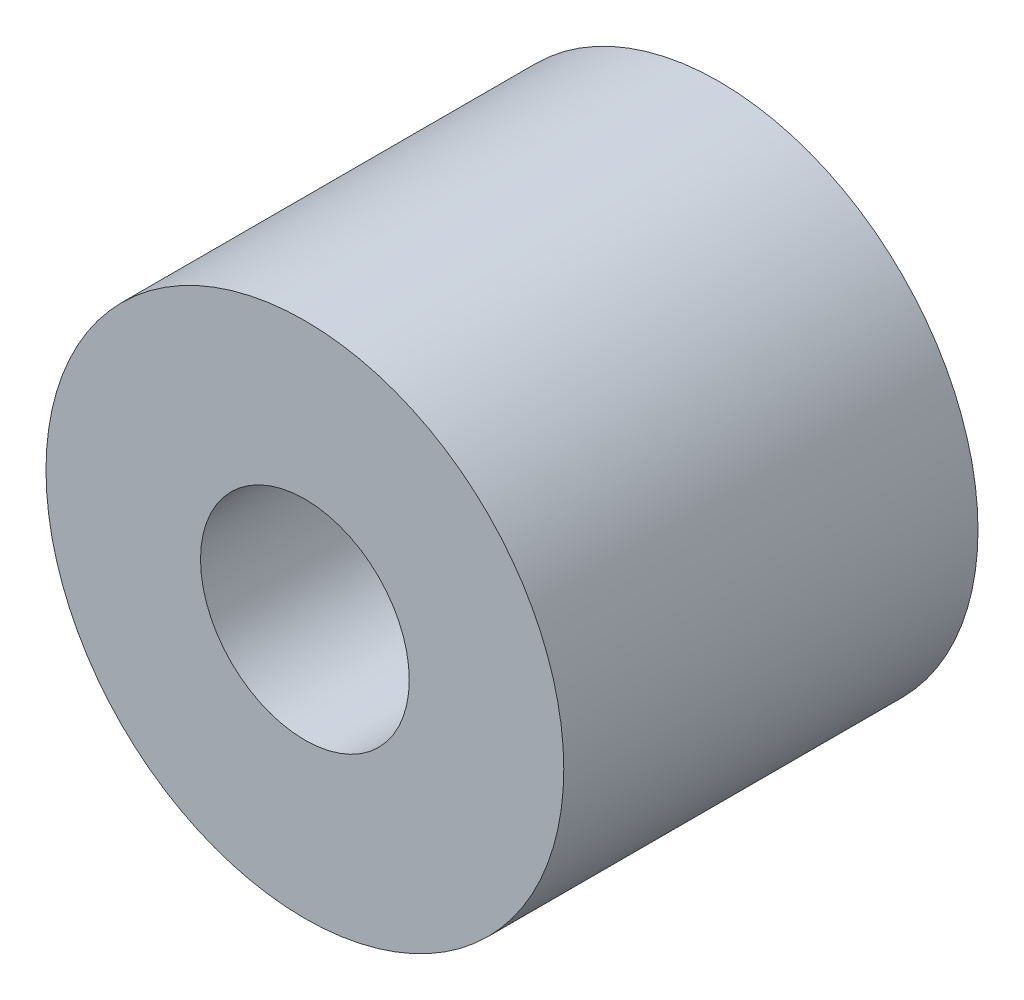
SolidWorks part; units mm, degrees
material "Nylon 101"
ref_plane "Front Plane" through (0, 0, 0) normal (0, 0, 1) x (1, 0, 0)
ref_plane "Top Plane" through (0, 0, 0) normal (0, 1, 0) x (1, 0, 0)
ref_plane "Right Plane" through (0, 0, 0) normal (1, 0, 0) x (0, 0, -1)
sketch "Sketch1" plane through (0, 0, 0) normal (0, 0, 1) x (1, 0, 0)
  circle A0 centre (0, 0) radius 7.9375
  circle A1 centre (0, 0) radius 3.2004
  dimension "OD" = 15.875
  dimension "ID" = 6.4008
extrude "Extrude1" add sketch "Sketch1" along normal mid plane 12.7
sketch "Sketch2" plane through (0, 0, 0) normal (1, 0, 0) x (0, 0, -1)
  line L0 (-6.35, -3.2004) -> (6.35, -3.2004) construction
  line L3 (6.35, 3.2004) -> (-6.35, 3.2004) construction
  line L5 (-6.35, -3.2004) -> (6.35, -3.2004)
  line L6 (6.35, 3.2004) -> (-6.35, 3.2004)
sketch "Sketch4" plane through (0, 0, 6.35) normal (0, 0, 1) x (1, 0, 0)
  line L0 (0, 0) -> (-2.263, 2.263)
  line L1 (0, -6.985) -> (0, 6.985) construction
  circle A0 centre (0, 0) radius 3.2004 construction
  dimension "D1" = 45
